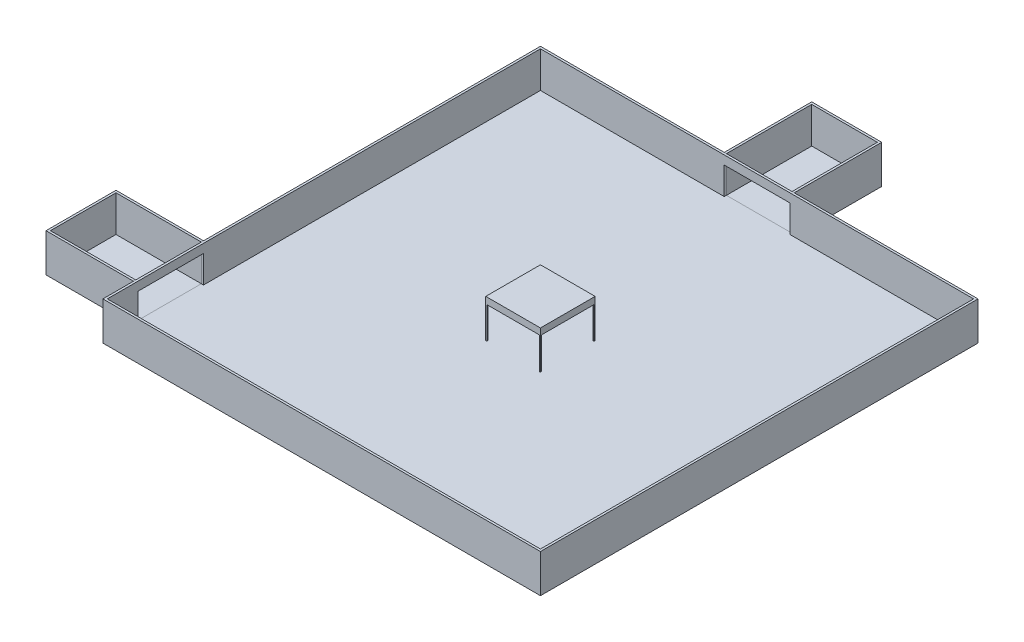
SolidWorks part; units mm, degrees
ref_plane "前视基准面" through (0, 0, 0) normal (0, 0, 1) x (1, 0, 0)
ref_plane "上视基准面" through (0, 0, 0) normal (0, 1, 0) x (1, 0, 0)
ref_plane "右视基准面" through (0, 0, 0) normal (1, 0, 0) x (0, 0, -1)
other "Configuration Table"
sketch "草图1" plane through (0, 0, 0) normal (0, 1, 0) x (1, 0, 0)
  line L0 (0, 0) -> (0, 4000)
  line L1 (0, 4000) -> (4000, 4000)
  line L2 (4000, 4000) -> (4000, 0)
  line L3 (4000, 0) -> (0, 0)
  dimension "D1" = 4000
  dimension "D2" = 4000
  dimension "D3" = 4000
extrude "凸台-拉伸1" add sketch "草图1" along normal blind 350 contours L3 L0 L1 L2
sketch "草图2" plane through (0, 350, 0) normal (0, 1, 0) x (1, 0, 0)
  line L0 (20, 3980) -> (3980, 3980)
  line L1 (3980, 3980) -> (3980, 20)
  line L2 (3980, 20) -> (20, 20)
  line L3 (20, 20) -> (20, 3980)
  line L4 (4000, 4000) -> (4000, 0) construction
  line L5 (0, 4000) -> (4000, 4000) construction
  line L6 (0, 0) -> (0, 4000) construction
  line L7 (4000, 0) -> (0, 0) construction
  dimension "D1" = 20
  dimension "D2" = 20
  dimension "D3" = 20
  dimension "D4" = 20
extrude "切除-拉伸1" cut sketch "草图2" against normal blind 330
sketch "草图3" plane through (0, 0, -4000) normal (0, 0, -1) x (-1, 0, 0)
  line L0 (-2000, 643.7534) -> (-2000, -168.5082) construction
  line L1 (-1700, 270) -> (-2300, 270)
  line L2 (-2300, 270) -> (-2300, 20)
  line L3 (-2300, 20) -> (-1700, 20)
  line L4 (-1700, 270) -> (-1700, 20)
  line L5 (0, 0) -> (-4000, 0) construction
  line L6 (0, 350) -> (0, 0) construction
  point P7 (-2000, 20)
  point P8 (-2000, 270)
  dimension "D1" = 600
  dimension "D2" = 250
  dimension "D3" = 20
  dimension "D4" = 1700
extrude "切除-拉伸2" cut sketch "草图3" against normal blind 20
sketch "草图5" plane through (0, 0, 0) normal (-1, 0, 0) x (0, 0, 1)
  line L0 (-600, 365.7553) -> (-600, -137.7591) construction
  line L1 (-300, 20) -> (-900, 20)
  line L2 (-900, 20) -> (-900, 270)
  line L3 (-900, 270) -> (-300, 270)
  line L4 (-300, 20) -> (-300, 270)
  line L5 (0, 0) -> (-4000, 0) construction
  line L6 (0, 350) -> (0, 0) construction
  point P2 (-600, 270)
  point P8 (-600, 20)
  dimension "D1" = 20
  dimension "D2" = 250
  dimension "D3" = 600
  dimension "D4" = 300
extrude "切除-拉伸3" cut sketch "草图5" against normal blind 20
sketch "草图6" plane through (0, 20, 0) normal (0, 1, 0) x (1, 0, 0)
  line L0 (4417.4375, 2000) -> (-502.2256, 2000) construction
  line L1 (2000, 4803.7985) -> (2000, -159.9476) construction
  line L2 (2250, 2250) -> (2250, 1750)
  line L3 (2250, 1750) -> (1750, 1750)
  line L4 (1750, 2250) -> (1750, 1750)
  line L5 (2250, 2250) -> (1750, 2250)
  line L6 (20, 20) -> (3980, 20) construction
  line L7 (3980, 3980) -> (20, 3980) construction
  line L8 (20, 3980) -> (20, 900) construction
  line L9 (3980, 20) -> (3980, 3980) construction
  point P9 (2000, 1750)
  point P10 (1750, 2000)
  point P11 (2250, 2000)
  dimension "D1" = 1730
  dimension "D2" = 1730
  dimension "D3" = 1730
  dimension "D4" = 1730
extrude "凸台-拉伸2" add sketch "草图6" along normal blind 350
sketch "草图8" plane through (0, 0, -1750) normal (0, 0, 1) x (1, 0, 0)
  line L0 (2000, -336.1411) -> (2000, 576.6479) construction
  line L2 (4000, 0) -> (0, 0) construction
  line L8 (1760, 310) -> (1760, 20)
  line L9 (1760, 20) -> (2240, 20)
  line L10 (1760, 310) -> (2240, 310)
  line L11 (2240, 310) -> (2240, 20)
  point P8 (2000, 310)
  point P9 (2000, 0)
  point P10 (2000, 310)
  point P12 (2000, 20)
  dimension "D1" = 20
  dimension "D2" = 480
  dimension "D3" = 290
extrude "切除-拉伸4" cut sketch "草图8" against normal blind 500
sketch "草图11" plane through (1750, 0, 0) normal (-1, 0, 0) x (0, 0, 1)
  line L0 (-2000, 620.6935) -> (-2000, -207.6525) construction
  line L1 (-1760, 20) -> (-2240, 20)
  line L2 (-2240, 20) -> (-2240, 310)
  line L3 (-2240, 310) -> (-1760, 310)
  line L4 (-1760, 20) -> (-1760, 310)
  line L5 (0, 0) -> (-4000, 0) construction
  line L7 (-4000, 350) -> (-4000, 0) construction
  point P7 (-2000, 20)
  point P8 (-2000, 310)
  dimension "D1" = 480
  dimension "D2" = 20
  dimension "D3" = 1760
  dimension "D4" = 290
extrude "切除-拉伸5" cut sketch "草图11" against normal blind 500
sketch "草图19" plane through (0, 0, 0) normal (0, -1, 0) x (1, 0, 0)
  line L0 (2000, -4648.259) -> (2000, 376.8578) construction
  line L1 (-800, -600) -> (4641.0633, -600) construction
  line L2 (4000, 0) -> (0, 0) construction
  line L3 (2320, -4000) -> (2320, -4800)
  line L4 (0, -4000) -> (4000, -4000) construction
  line L5 (2320, -4800) -> (1680, -4800)
  line L6 (1680, -4800) -> (1680, -4000)
  line L7 (1680, -4000) -> (2320, -4000)
  line L8 (0, 0) -> (0, -4000) construction
  line L9 (4000, -4000) -> (4000, 0) construction
  line L10 (0, -920) -> (-800, -920)
  line L11 (-800, -920) -> (-800, -280)
  line L12 (-800, -280) -> (0, -280)
  line L13 (0, -280) -> (0, -920)
  dimension "D1" = 600
  dimension "D2" = 1680
  dimension "D3" = 1680
  dimension "D4" = 800
  dimension "D5" = 280
  dimension "D6" = 640
  dimension "D7" = 800
extrude "凸台-拉伸10" add sketch "草图19" against normal blind 350 separate body
sketch "草图20" plane through (0, 350, 0) normal (0, 1, 0) x (1, 0, 0)
  line L0 (2300, 4000) -> (1700, 4000)
  line L1 (1700, 4000) -> (1700, 4780)
  line L2 (1700, 4780) -> (2300, 4780)
  line L3 (2300, 4780) -> (2300, 4000)
  line L4 (3980, 3980) -> (20, 3980) construction
  line L5 (1680, 4000) -> (1680, 4800) construction
  line L6 (2320, 4800) -> (2320, 4000) construction
  line L7 (1680, 4800) -> (2320, 4800) construction
  line L8 (0, 900) -> (0, 300)
  line L9 (0, 300) -> (-780, 300)
  line L10 (-780, 300) -> (-780, 900)
  line L11 (-780, 900) -> (0, 900)
  line L12 (20, 3980) -> (20, 20) construction
  line L13 (-800, 920) -> (0, 920) construction
  line L14 (0, 280) -> (-800, 280) construction
  line L15 (-800, 280) -> (-800, 920) construction
  dimension "D1" = 20
  dimension "D2" = 20
  dimension "D3" = 20
  dimension "D4" = 20
  dimension "D5" = 20
  dimension "D6" = 20
  dimension "D7" = 20
  dimension "D8" = 20
extrude "切除-拉伸7" cut sketch "草图20" against normal blind 330
